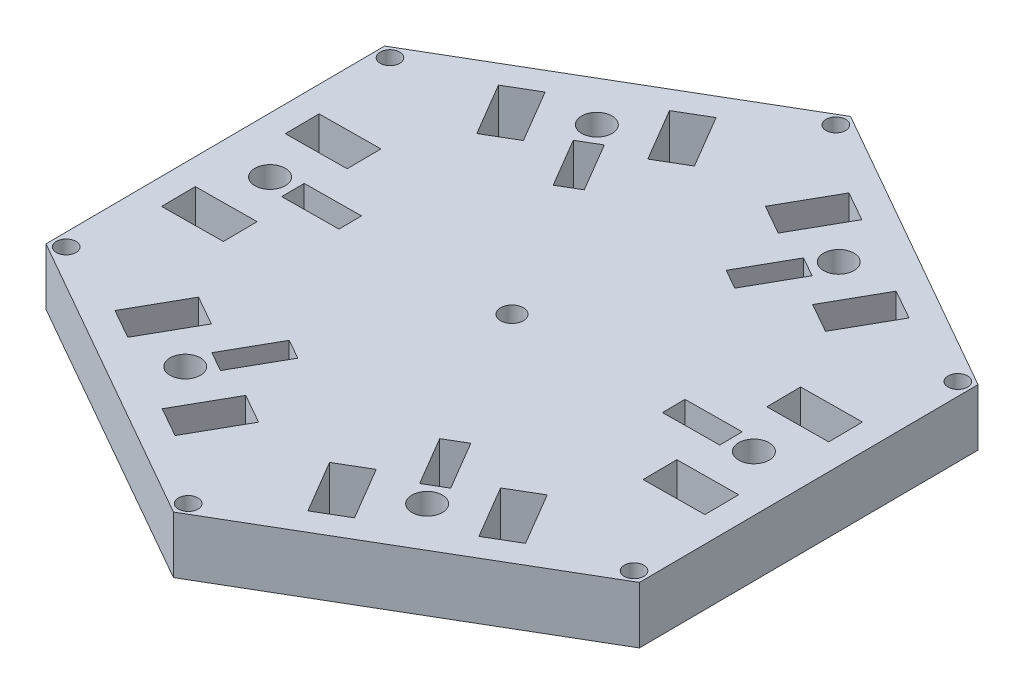
SolidWorks part; units mm, degrees
ref_plane "Front Plane" through (0, 0, 0) normal (0, 0, 1) x (1, 0, 0)
ref_plane "Top Plane" through (0, 0, 0) normal (0, 1, 0) x (1, 0, 0)
ref_plane "Right Plane" through (0, 0, 0) normal (1, 0, 0) x (0, 0, -1)
sketch "Sketch1" plane through (0, 0, 0) normal (0, 1, 0) x (1, 0, 0)
  line L0 (3.7154, 24.6289) -> (7.0318, 22.7534)
  line L7 (21.8831, 12.8954) -> (-0.2262, 25.399)
  line L8 (-0.2262, 25.399) -> (-22.1093, 12.5036)
  line L9 (-22.1093, 12.5036) -> (-21.8831, -12.8954)
  line L10 (-21.8831, -12.8954) -> (0.2262, -25.399)
  line L11 (0.2262, -25.399) -> (22.1093, -12.5036)
  line L12 (22.1093, -12.5036) -> (21.8831, 12.8954)
  line L13 (32.8819, 19.2455) -> (-0.2262, 38.0993)
  line L14 (-0.2262, 38.0993) -> (-33.1081, 18.8538)
  line L15 (-33.1081, 18.8538) -> (-32.8819, -19.2455)
  line L16 (-32.8819, -19.2455) -> (0.2262, -38.0993)
  line L17 (0.2262, -38.0993) -> (33.1081, -18.8538)
  line L18 (33.1081, -18.8538) -> (32.8819, 19.2455)
  line L19 (10.4078, 28.7229) -> (7.0318, 22.7534)
  line L20 (7.0914, 30.5984) -> (10.4078, 28.7229)
  line L25 (-10.9176, 28.533) -> (-7.4359, 22.6245)
  line L26 (-7.6351, 30.4673) -> (-10.9176, 28.533)
  line L27 (-4.1534, 24.5588) -> (-7.6351, 30.4673)
  line L30 (3.7154, 24.6289) -> (7.0914, 30.5984)
  line L31 (15.8755, 17.7519) -> (19.1919, 15.8764)
  line L32 (19.1919, 15.8764) -> (22.5679, 21.8459)
  line L33 (22.5679, 21.8459) -> (19.2515, 23.7214)
  line L34 (19.2515, 23.7214) -> (15.8755, 17.7519)
  line L35 (23.187, 9.0968) -> (23.2209, 5.287)
  line L36 (30.0786, 5.348) -> (23.2209, 5.287)
  line L37 (30.0447, 9.1579) -> (30.0786, 5.348)
  line L38 (23.187, 9.0968) -> (30.0447, 9.1579)
  line L39 (-11.1677, 18.9513) -> (-16.0679, 27.2669) construction
  line L40 (-0.2262, 25.399) -> (-2.4173, 29.1173) construction
  line L41 (-19.4716, 15.5321) -> (-16.1891, 17.4664)
  line L44 (-19.4716, 15.5321) -> (-22.9533, 21.4405)
  line L45 (-22.9533, 21.4405) -> (-19.6708, 23.3748)
  line L46 (-19.6708, 23.3748) -> (-16.1891, 17.4664)
  line L49 (-7.4359, 22.6245) -> (-4.1534, 24.5588)
  line L50 (23.3114, -4.8726) -> (23.3453, -8.6825)
  line L51 (23.3453, -8.6825) -> (30.203, -8.6214)
  line L52 (30.203, -8.6214) -> (30.1691, -4.8116)
  line L53 (30.1691, -4.8116) -> (23.3114, -4.8726)
  line L54 (19.4716, -15.5321) -> (16.1891, -17.4664)
  line L55 (19.6708, -23.3748) -> (16.1891, -17.4664)
  line L56 (22.9533, -21.4405) -> (19.6708, -23.3748)
  line L57 (19.4716, -15.5321) -> (22.9533, -21.4405)
  line L58 (7.4359, -22.6245) -> (4.1534, -24.5588)
  line L59 (4.1534, -24.5588) -> (7.6351, -30.4673)
  line L60 (7.6351, -30.4673) -> (10.9176, -28.533)
  line L61 (10.9176, -28.533) -> (7.4359, -22.6245)
  line L62 (-3.7154, -24.6289) -> (-7.0318, -22.7534)
  line L63 (-10.4078, -28.7229) -> (-7.0318, -22.7534)
  line L64 (-7.0914, -30.5984) -> (-10.4078, -28.7229)
  line L65 (-3.7154, -24.6289) -> (-7.0914, -30.5984)
  line L66 (-15.8755, -17.7519) -> (-19.1919, -15.8764)
  line L67 (-19.1919, -15.8764) -> (-22.5679, -21.8459)
  line L68 (-22.5679, -21.8459) -> (-19.2515, -23.7214)
  line L69 (-19.2515, -23.7214) -> (-15.8755, -17.7519)
  line L70 (-23.187, -9.0968) -> (-23.2209, -5.287)
  line L71 (-30.0786, -5.348) -> (-23.2209, -5.287)
  line L72 (-30.0447, -9.1579) -> (-30.0786, -5.348)
  line L73 (-23.187, -9.0968) -> (-30.0447, -9.1579)
  line L74 (-23.3114, 4.8726) -> (-23.3453, 8.6825)
  line L75 (-23.3453, 8.6825) -> (-30.203, 8.6214)
  line L76 (-30.203, 8.6214) -> (-30.1691, 4.8116)
  line L77 (-30.1691, 4.8116) -> (-23.3114, 4.8726)
  line L102 (-13.4224, 20.276) -> (-11.2341, 21.5656)
  line L103 (-11.2341, 21.5656) -> (-8.0103, 16.0948)
  line L104 (-8.0103, 16.0948) -> (-10.1986, 14.8053)
  line L105 (-10.1986, 14.8053) -> (-13.4224, 20.276)
  line L106 (10.8483, 21.7622) -> (13.0593, 20.5118)
  line L107 (13.0593, 20.5118) -> (9.9333, 14.9845)
  line L108 (9.9333, 14.9845) -> (7.7224, 16.2349)
  line L109 (7.7224, 16.2349) -> (10.8483, 21.7622)
  line L110 (24.2708, 1.4862) -> (24.2934, -1.0537)
  line L111 (24.2934, -1.0537) -> (17.9436, -1.1103)
  line L112 (17.9436, -1.1103) -> (17.921, 1.4296)
  line L113 (17.921, 1.4296) -> (24.2708, 1.4862)
  line L114 (13.4224, -20.276) -> (11.2341, -21.5656)
  line L115 (11.2341, -21.5656) -> (8.0103, -16.0948)
  line L116 (8.0103, -16.0948) -> (10.1986, -14.8053)
  line L117 (10.1986, -14.8053) -> (13.4224, -20.276)
  line L118 (-10.8483, -21.7622) -> (-13.0593, -20.5118)
  line L119 (-13.0593, -20.5118) -> (-9.9333, -14.9845)
  line L120 (-9.9333, -14.9845) -> (-7.7224, -16.2349)
  line L121 (-7.7224, -16.2349) -> (-10.8483, -21.7622)
  line L122 (-24.2708, -1.4862) -> (-24.2934, 1.0537)
  line L123 (-24.2934, 1.0537) -> (-17.9436, 1.1103)
  line L124 (-17.9436, 1.1103) -> (-17.921, -1.4296)
  line L125 (-17.921, -1.4296) -> (-24.2708, -1.4862)
  line L127 (15.7326, 9.3444) -> (-0.2262, 18.297)
  line L128 (-0.2262, 18.297) -> (-15.9587, 8.9526)
  line L129 (-15.9587, 8.9526) -> (-15.7326, -9.3444)
  line L130 (-15.7326, -9.3444) -> (0.2262, -18.297)
  line L131 (0.2262, -18.297) -> (15.9587, -8.9526)
  line L132 (15.9587, -8.9526) -> (15.7326, 9.3444)
  line L133 (-33.1081, 18.8538) -> (-22.1093, 12.5036) construction
  circle A0 centre (0, 0) radius 32.9956 construction
  circle A1 centre (0, 0) radius 21.997 construction
  circle A2 centre (-13.6178, 23.1091) radius 1.7
  circle A3 centre (13.2042, 23.3479) radius 1.7
  circle A4 centre (0, 0) radius 21.997 construction
  circle A5 centre (26.822, 0.2388) radius 1.7
  circle A6 centre (0, 0) radius 21.997 construction
  circle A7 centre (13.6178, -23.1091) radius 1.7
  circle A8 centre (0, 0) radius 21.997 construction
  circle A9 centre (-13.2042, -23.3479) radius 1.7
  circle A10 centre (0, 0) radius 21.997 construction
  circle A11 centre (-26.822, -0.2388) radius 1.7
  circle A12 centre (0, 0) radius 21.997 construction
  circle A13 centre (0, 0) radius 21.997 construction
  circle A14 centre (0, 0) radius 21.997 construction
  circle A15 centre (0, 0) radius 21.997 construction
  circle A16 centre (0, 0) radius 21.997 construction
  circle A17 centre (0, 0) radius 21.997 construction
  circle A18 centre (0, 0) radius 1.27
  circle A19 centre (0, 0) radius 21.997 construction
  circle A20 centre (0, 0) radius 21.997 construction
  circle A21 centre (0, 0) radius 21.997 construction
  circle A22 centre (0, 0) radius 21.997 construction
  circle A23 centre (0, 0) radius 21.997 construction
  circle A24 centre (0, 0) radius 15.8469 construction
  circle A25 centre (-31.6783, 18.0283) radius 1.0922
  circle A26 centre (-0.2262, 36.4483) radius 1.0922
  circle A27 centre (0, 0) radius 32.9956 construction
  circle A28 centre (31.4521, 18.42) radius 1.0922
  circle A29 centre (0, 0) radius 32.9956 construction
  circle A30 centre (31.6783, -18.0283) radius 1.0922
  circle A31 centre (0, 0) radius 32.9956 construction
  circle A32 centre (0.2262, -36.4483) radius 1.0922
  circle A33 centre (0, 0) radius 32.9956 construction
  circle A34 centre (-31.4521, -18.42) radius 1.0922
  circle A35 centre (0, 0) radius 32.9956 construction
  point P58 (-15.0363, 25.5162)
  point P88 (0, 0)
  point P89 (-12.3283, 20.9208)
  point P92 (-13.0593, 22.2338)
  point P119 (0, 0)
  point P129 (0, 0)
  point P151 (0, 0)
  dimension "D17" = 3.4
  dimension "D6" = 3.4
  dimension "D13" = 2.286
  dimension "D19" = 2.54
  dimension "D21" = 2.1844
  dimension "D2" = 25.4
  dimension "D3" = 6
  dimension "D4" = 25.399
  dimension "D5" = 5.08
  dimension "D7" = 3.81
  dimension "D8" = 6.858
  dimension "D9" = 3.81
  dimension "D10" = 3.302
  dimension "D11" = 1.27
  dimension "D12" = 6
  dimension "D14" = 6.35
  dimension "D15" = 6
  dimension "D18" = 6.3502
  dimension "D16" = 2.54
  dimension "D20" = 18.297
  dimension "D22" = 1.651
  dimension "D23" = 6
extrude "Boss-Extrude1" add sketch "Sketch1" against normal blind 6.35 contours L17 L18 L13 L14 L15 L16 A11 A9 A7 A5 A3 A2 L77 L76 L75 L74 L69 L68 L67 L66 L61 L60 L59 L58 L53 L52 L51 L50 L49 L25 L26 L27 L34 L33 L32 L31 L0 L30 | L124 L125 L9 L10 L119 L120 L121 L11 L115 L116 L117 L12 L111 L112 L113 L7 L107 L108 L109 L8 L103 L104 L105 L123 L132 L131 L130 L129 L128 L127 | L131 L132 L127 L128 L129 L130 A18 region at (21.2605, 0, -7.1746) region at (31.9855, 0, -0.1899) region at (15.3601, 0, -0.1899)
